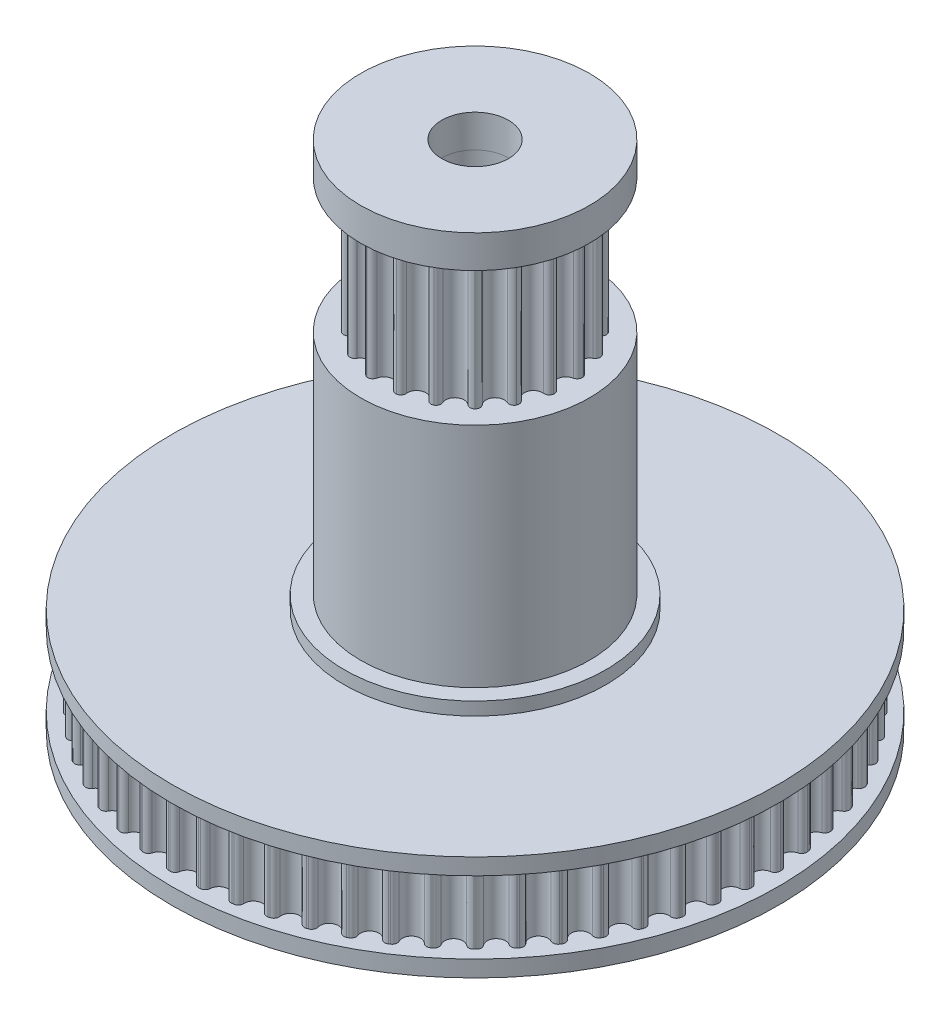
SolidWorks part; units mm, degrees
ref_plane "Front Plane" through (0, 0, 0) normal (0, 0, 1) x (1, 0, 0)
ref_plane "Top Plane" through (0, 0, 0) normal (0, 1, 0) x (1, 0, 0)
ref_plane "Right Plane" through (0, 0, 0) normal (1, 0, 0) x (0, 0, -1)
sketch "PulleyOffsets" plane through (0, 0, 0) normal (1, 0, 0) x (0, 0, -1)
  line L0 (17.4625, 0) -> (-17.4625, 0) construction
  line L1 (17.4625, 34.925) -> (-17.4625, 34.925) construction
  line L2 (0, 0) -> (0, 34.925) construction
  point P7 (0, 0)
  dimension "D1" = 34.925
ref_axis "Axis1" through (0, 34.9332, 0) along (0, -1, 0)
ref_plane "Big Pulley Plane" through (0, 0, 0) normal (0, 1, 0) x (1, 0, 0)
ref_plane "Small Pulley Plane" through (0, 34.925, 0) normal (0, 1, 0) x (1, 0, 0)
sketch "Sketch1" plane through (0, 0, 0) normal (0, 1, 0) x (1, 0, 0)
  line L0 (0, 0) -> (0, 28.2667) construction
  line L1 (0, 0) -> (2.9202, 27.7837) construction
  circle A0 centre (0, 0) radius 28.2667 construction
  circle A1 centre (0, 0) radius 27.0467 construction
  circle A2 centre (0, 27.9367) radius 0.89 construction
  circle A5 centre (2.9202, 27.7837) radius 0.89 construction
  arc A6 (0, 27.0467) -> (0.8804, 27.8061) centre (0, 27.9367) ccw
  arc A7 (0.8804, 27.8061) -> (1.3997, 28.2321) centre (1.3749, 27.7327) cw
  arc A8 (1.559, 28.2237) -> (2.031, 27.7458) centre (1.5314, 27.7245) cw
  arc A9 (2.8272, 26.8986) -> (2.031, 27.7458) centre (2.9202, 27.7837) cw
  arc A10 (1.3997, 28.2321) -> (1.559, 28.2237) centre (0, 0) cw
  arc A11 (0, 27.0467) -> (2.8272, 26.8986) centre (0, 0) ccw
  dimension "D1" = 56.5335
  dimension "D3" = 1.78
  dimension "D4" = 0.5
  dimension "D2" = 1.22
  dimension "D5" = 6
extrude "Boss-Extrude1" add sketch "Sketch1" along normal mid plane 7.112 contours A6 A11 A9 A8 A7 region at (0.001, 0, -0.0192)
pattern_circular "CirPattern1" count 60 over 360 about axis through (0, 34.9332, 0) along (0, -1, 0) of "Boss-Extrude1"
sketch "Sketch2" plane through (0, 0, 0) normal (1, 0, 0) x (0, 0, -1)
  line L10 (0, 3.5) -> (29.4415, 3.5) construction
  line L11 (0, 3.5) -> (0, 5.0875) construction
  line L12 (0, 5.0875) -> (29.4415, 5.0875) construction
  line L15 (29.4415, 3.5) -> (29.4415, 5.0875) construction
  line L20 (0, 34.9332) -> (0, -6.9932) construction
  line L22 (29.4415, 5.0875) -> (0, 5.0875)
  line L23 (29.4415, 5.0875) -> (29.4415, 3.5)
  line L24 (29.4415, 3.5) -> (0, 3.5)
  line L25 (0, 5.0875) -> (0, 3.5)
  dimension "D1" = 1.5875
  dimension "D2" = 29.4415
  dimension "D3" = 3.5
revolve "Revolve3" add sketch "Sketch2" angle 360 about axis through (0, 34.9332, 0) along (0, -1, 0) region at (0, 4.2937, -14.7207)
mirror "Mirror1" about plane through (0, 0, 0) normal (0, 1, 0) of "Revolve3"
sketch "Sketch3" plane through (0, 0, 0) normal (0, 1, 0) x (1, 0, 0)
  circle A0 centre (0, 0) radius 22.225
  dimension "D1" = 44.45
extrude "Cut-Extrude1" [suppressed] cut sketch "Sketch3" against normal through all both and the other way through all
sketch "Sketch6" plane through (0, 0, 0) normal (0, 1, 0) x (1, 0, 0)
  line L0 (0, 0) -> (0, 9.1676) construction
  line L1 (0, 0) -> (2.731, 8.405) construction
  circle A0 centre (0, 0) radius 9.1676 construction
  circle A1 centre (0, 0) radius 7.9476 construction
  circle A2 centre (0, 8.8376) radius 0.89 construction
  circle A5 centre (2.731, 8.405) radius 0.89 construction
  arc A6 (0, 7.9476) -> (0.8721, 8.6598) centre (0, 8.8376) ccw
  arc A7 (0.8721, 8.6598) -> (1.4405, 9.0537) centre (1.362, 8.5599) cw
  arc A8 (1.4277, 9.0557) -> (1.8466, 8.5054) centre (1.3498, 8.5618) cw
  arc A9 (2.4559, 7.5586) -> (1.8466, 8.5054) centre (2.731, 8.405) cw
  arc A10 (1.4405, 9.0537) -> (1.4277, 9.0557) centre (0, 0) cw construction
  arc A11 (0, 7.9476) -> (2.4559, 7.5586) centre (0, 0) ccw
  arc A12 (1.4405, 9.0537) -> (1.4277, 9.0557) centre (0, 0) cw
  dimension "D3" = 1.78
  dimension "D4" = 0.5
  dimension "D2" = 1.22
  dimension "D1" = 18.3352
  dimension "D5" = 18
extrude "Boss-Extrude2" add sketch "Sketch6" along normal mid plane 13 from surface contours A6 A11 A9 A8 A7 region at (0.0089, 0, -0.0564) starting at plane "Small Pulley Plane"
pattern_circular "CirPattern2" count 20 over 360 about axis through (0, 34.9332, 0) along (0, -1, 0) of "Boss-Extrude2"
sketch "Sketch4" plane through (0, 0, 0) normal (0, 0, 1) x (1, 0, 0)
  line L0 (12.7, 5.0875) -> (-12.7, 5.0875) construction
  line L1 (29.4415, 5.0875) -> (-29.4415, 5.0875) construction
  line L2 (-12.7, 5.0875) -> (-12.7, 6.3575)
  line L3 (-12.7, 6.3575) -> (-11.1125, 6.3575)
  line L4 (-11.1125, 6.3575) -> (-11.1125, 28.425)
  line L5 (0, 0) -> (0, 44.6) construction
  line L6 (11.1125, 6.3575) -> (11.1125, 28.425) construction
  line L7 (12.7, 6.3575) -> (11.1125, 6.3575) construction
  line L8 (12.7, 5.0875) -> (12.7, 6.3575) construction
  line L9 (-11.1125, 28.425) -> (11.1125, 28.425) construction
  line L10 (-12.7, 5.0875) -> (0, 5.0875)
  line L11 (0, 5.0875) -> (0, 28.425)
  line L12 (0, 28.425) -> (-11.1125, 28.425)
  line L13 (1.841, 28.425) -> (3.5054, 28.425) construction
  line L14 (0.8721, 41.425) -> (-0.8721, 41.425) construction
  line L15 (-11.1125, 44.6) -> (0, 44.6)
  line L16 (-11.1125, 44.6) -> (-11.1125, 41.425)
  line L17 (-11.1125, 41.425) -> (0, 41.425)
  line L18 (0, 44.6) -> (0, 41.425)
  line L19 (-11.1125, 28.425) -> (-11.1125, 41.425) construction
  point P14 (0, 5.0875)
  dimension "D1" = 1.27
  dimension "D2" = 25.4
  dimension "D3" = 22.225
  dimension "D4" = 3.175
revolve "Revolve4" add sketch "Sketch4" angle 360 about L11
sketch "Sketch7" plane through (0, 44.6, 0) normal (0, 1, 0) x (1, 0, 0)
  circle A0 centre (0, 0) radius 3.2385
  dimension "D1" = 6.477
extrude "Cut-Extrude2" cut sketch "Sketch7" against normal through all both and the other way through all
sketch "Sketch8" plane through (0, -5.0875, 0) normal (0, -1, 0) x (1, 0, 0)
  circle A0 centre (0, 0) radius 4.7625
  dimension "D1" = 9.525
equation "\"TEETH_NUM\"= 60"
equation "\"TOOTH_PITCH\"= 3mm"
equation "\"PITCH_LINE_OFFSET\"= .015in"
equation "\"DIAMETER_PER_GROOVE\"= \"OUTSIDE_DIAMETER\" / \"TEETH_NUM\" * 1in"
equation "\"PITCH_DIAMETER\"= ( ( \"TEETH_NUM\" * 3 - 1.31 ) / 3.1415 + .415 ) * 1mm"
equation "\"OUTSIDE_DIAMETER\"= \"PITCH_DIAMETER\" - \"PITCH_LINE_OFFSET\" * 2"
equation "\"D1@Sketch1\"=\"OUTSIDE_DIAMETER\""
equation "\"TOOTH_HEIGHT\"= 1.22mm"
equation "\"D2@Sketch1\"=\"TOOTH_HEIGHT\""
equation "\"TOOTH_DIAMETER\"= 1.78mm"
equation "\"INTERNAL_RADIUS\"= .5mm"
equation "\"D3@Sketch1\"=\"TOOTH_DIAMETER\""
equation "\"D5@Sketch1\"=360 / \"TEETH_NUM\""
equation "\"D4@Sketch1\"=\"INTERNAL_RADIUS\""
equation "\"D1@CirPattern1\"=\"TEETH_NUM\""
equation "\"BELT_GAP\"= 7mm"
equation "\"D2@Sketch2\"=\"PITCH_DIAMETER\"/2+1/32"
equation "\"D3@Sketch2\"=\"BELT_GAP\"/2"
equation "\"2_TEETH_NUM\"= 20"
equation "\"2_PITCH_DIAMETER\"= ( ( \"2_TEETH_NUM\" * 3 - 1.31 ) / 3.1415 + .415 ) * 1mm"
equation "\"2_OUTSIDE_DIAMETER\"= \"2_PITCH_DIAMETER\" - \"PITCH_LINE_OFFSET\" * 2"
equation "\"2_DIAMETER_PER_GROOVE\"= \"2_OUTSIDE_DIAMETER\" / \"2_TEETH_NUM\" * 1in"
equation "\"D5@Sketch6\"=360/\"2_TEETH_NUM\""
equation "\"D1@Sketch6\"=\"2_OUTSIDE_DIAMETER\""
equation "\"D2@Sketch6\"=\"TOOTH_HEIGHT\""
equation "\"D3@Sketch6\"=\"TOOTH_DIAMETER\""
equation "\"D4@Sketch6\"=\"INTERNAL_RADIUS\""
equation "\"2_BELT_GAP\"= 13mm"
equation "\"D1@CirPattern2\"=\"2_TEETH_NUM\""
equation "\"D1@Boss-Extrude2\"=\"2_BELT_GAP\""
equation "\"Pulley_OffSets\"= 1.375"
equation "\"D1@PulleyOffsets\" = \"Pulley_OffSets\""
